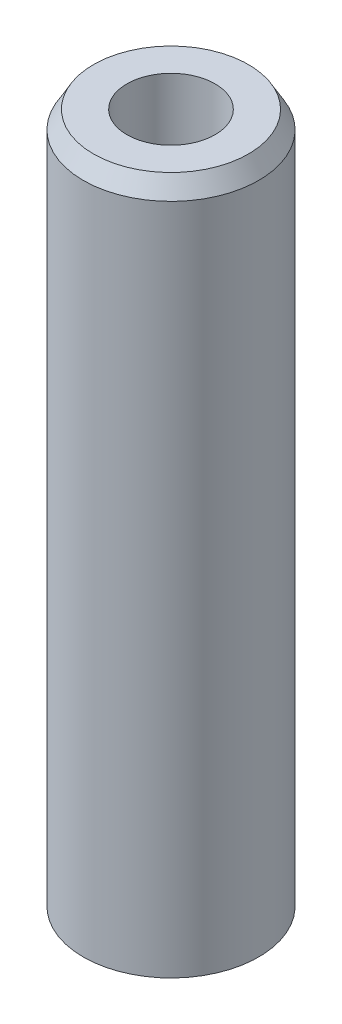
SolidWorks part; units mm, degrees
ref_plane "Front Plane" through (0, 0, 0) normal (0, 0, 1) x (1, 0, 0)
ref_plane "Top Plane" through (0, 0, 0) normal (0, 1, 0) x (1, 0, 0)
ref_plane "Right Plane" through (0, 0, 0) normal (1, 0, 0) x (0, 0, -1)
sketch "Sketch1" plane through (0, 0, 0) normal (0, 1, 0) x (1, 0, 0)
  circle A0 centre (0, 0) radius 7.5
  dimension "SHAFT_OD" = 15
extrude "Boss-Extrude1" add sketch "Sketch1" along normal blind 59.881
sketch "Sketch2" plane through (0, 0, 0) normal (0, 1, 0) x (1, 0, 0)
  circle A0 centre (0, 0) radius 3.77
  dimension "BORE_D" = 7.5399
extrude "Cut-Extrude1" cut sketch "Sketch2" along normal through all
chamfer "Chamfer1" distance 1.5175 angle 30 2 edges at (0, 59.881, 7.5) (0, 0, 7.5) first distance on face at (0, 59.881, 7.5) first distance on face at (0, 0, 3.77)
